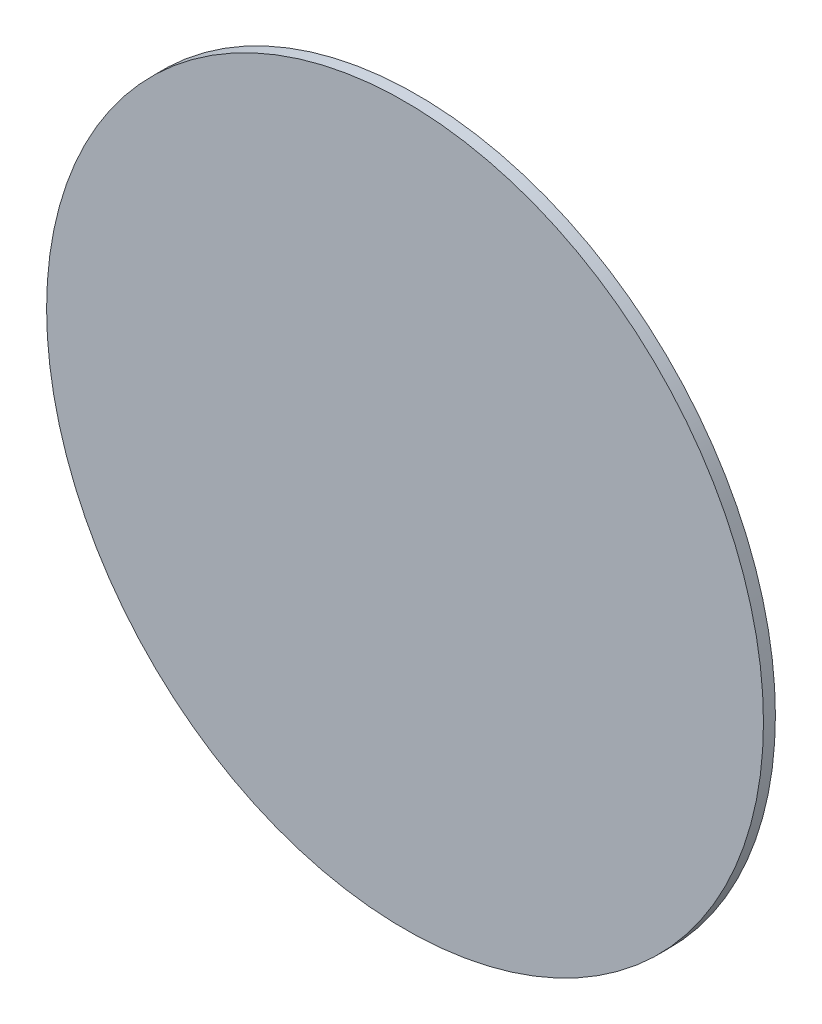
SolidWorks part; units mm, degrees
material "Maple"
ref_plane "Front Plane" through (0, 0, 0) normal (0, 0, 1) x (1, 0, 0)
ref_plane "Top Plane" through (0, 0, 0) normal (0, 1, 0) x (1, 0, 0)
ref_plane "Right Plane" through (0, 0, 0) normal (1, 0, 0) x (0, 0, -1)
sketch "Sketch1" plane through (0, 0, 0) normal (0, 0, 1) x (1, 0, 0)
  circle A0 centre (0, 0) radius 381
  dimension "D1" = 762
extrude "Boss-Extrude1" add sketch "Sketch1" along normal blind 12.7
